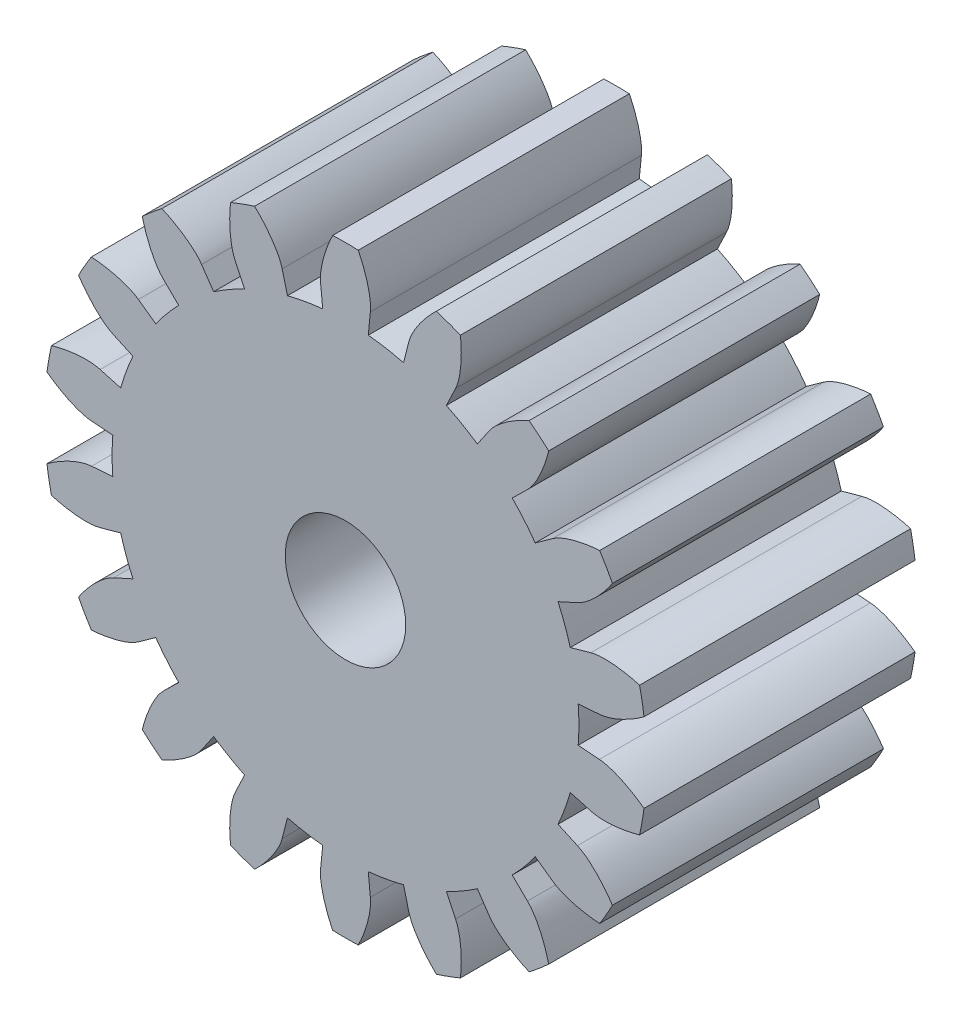
SolidWorks part; units mm, degrees
ref_plane "前视基准面" through (0, 0, 0) normal (0, 0, 1) x (1, 0, 0)
ref_plane "上视基准面" through (0, 0, 0) normal (0, 1, 0) x (1, 0, 0)
ref_plane "右视基准面" through (0, 0, 0) normal (1, 0, 0) x (0, 0, -1)
other "Configuration Table"
sketch "草图1" plane through (0, 0, 0) normal (0, 0, 1) x (1, 0, 0)
  line L0 (0, 0) -> (4.5, 0) construction
  line L1 (0, 0) -> (4.4829, 0.3922) construction
  line L2 (0, 0) -> (4.2162, 0.3242)
  line L3 (4.4829, 0.3922) -> (4.4829, -0.3922) construction
  line L4 (0, 0) -> (4.2162, -0.3242)
  circle A0 centre (0, 0) radius 5
  circle A1 centre (0, 0) radius 4.5 construction
  circle A2 centre (0, 0) radius 3.875
  circle A3 centre (0, 0) radius 4.2286 construction
  circle A4 centre (0, 0) radius 1
  spline S0 degree 4 poles (4.2162, 0.3242) (4.2483, 0.3267) (4.3375, 0.3403) (4.5024, 0.3926) (4.7554, 0.5133) (5.0556, 0.719) (5.3996, 1.035) (5.7429, 1.4621) (6.0488, 1.9801) (6.3604, 2.7282) (6.5454, 3.5193) (6.6174, 4.3594) (6.5658, 5.3616) (6.386, 6.3504) (6.0115, 7.457) (5.4105, 8.6071) (4.6509, 9.6584) (3.7565, 10.5972) (2.7501, 11.414) (1.6521, 12.1025) (0.4824, 12.659) (-0.5894, 13.0292) (-1.4522, 13.2437) (-2.0892, 13.3611) (-2.4865, 13.4209) (-2.8127, 13.4604) (-3.1237, 13.492) (-3.465, 13.5153) (-3.7294, 13.5295) (-4.0312, 13.5361) (-4.338, 13.5384) (-4.6432, 13.533) (-5.1827, 13.5111) (-5.559, 13.4725) (-5.9997, 13.426) (-6.2265, 13.3891) (-6.3687, 13.3688) (-6.431, 13.3583) knots 0 0 0 0 0 0.005604 0.015718 0.02996 0.048734 0.068727 0.096889 0.125051 0.153212 0.209535 0.237696 0.271429 0.327752 0.384075 0.440398 0.496721 0.553044 0.609367 0.66569 0.722013 0.778336 0.806497 0.820578 0.834659 0.84874 0.86282 0.876901 0.890982 0.900036 0.909091 0.931818 0.954545 0.977273 0.988636 1 1 1 1 1 construction
  spline S1 degree 4 poles (4.2162, 0.3242) (4.2483, 0.3267) (4.3375, 0.3403) (4.5024, 0.3926) (4.7554, 0.5133) (5.0556, 0.719) (5.3996, 1.035) (5.7429, 1.4621) (6.0488, 1.9801) (6.3604, 2.7282) (6.5454, 3.5193) (6.6174, 4.3594) (6.5658, 5.3616) (6.386, 6.3504) (6.0115, 7.457) (5.4105, 8.6071) (4.6509, 9.6584) (3.7565, 10.5972) (2.7501, 11.414) (1.6521, 12.1025) (0.4824, 12.659) (-0.5894, 13.0292) (-1.4522, 13.2437) (-2.0892, 13.3611) (-2.4865, 13.4209) (-2.8127, 13.4604) (-3.1237, 13.492) (-3.465, 13.5153) (-3.7294, 13.5295) (-4.0312, 13.5361) (-4.2111, 13.5375) (-4.3059, 13.5372) (-4.3531, 13.5368) knots 0 0 0 0 0 0.005604 0.015718 0.02996 0.048734 0.068727 0.096889 0.125051 0.153212 0.209535 0.237696 0.271429 0.327752 0.384075 0.440398 0.496721 0.553044 0.609367 0.66569 0.722013 0.778336 0.806497 0.820578 0.834659 0.84874 0.86282 0.876901 0.890982 0.900036 0.909091 0.909091 0.909091 0.909091 0.909091
  spline S2 degree 4 poles (4.2162, -0.3242) (4.2483, -0.3267) (4.3375, -0.3403) (4.5024, -0.3926) (4.7554, -0.5133) (5.0556, -0.719) (5.3996, -1.035) (5.7429, -1.4621) (6.0488, -1.9801) (6.3604, -2.7282) (6.5454, -3.5193) (6.6174, -4.3594) (6.5658, -5.3616) (6.386, -6.3504) (6.0115, -7.457) (5.4105, -8.6071) (4.6509, -9.6584) (3.7565, -10.5972) (2.7501, -11.414) (1.6521, -12.1025) (0.4824, -12.659) (-0.5894, -13.0292) (-1.4522, -13.2437) (-2.0892, -13.3611) (-2.4865, -13.4209) (-2.8127, -13.4604) (-3.1237, -13.492) (-3.465, -13.5153) (-3.7294, -13.5295) (-4.0312, -13.5361) (-4.338, -13.5384) (-4.6432, -13.533) (-5.1827, -13.5111) (-5.559, -13.4725) (-5.9997, -13.426) (-6.2265, -13.3891) (-6.3687, -13.3688) (-6.431, -13.3583) knots 0 0 0 0 0 0.005604 0.015718 0.02996 0.048734 0.068727 0.096889 0.125051 0.153212 0.209535 0.237696 0.271429 0.327752 0.384075 0.440398 0.496721 0.553044 0.609367 0.66569 0.722013 0.778336 0.806497 0.820578 0.834659 0.84874 0.86282 0.876901 0.890982 0.900036 0.909091 0.931818 0.954545 0.977273 0.988636 1 1 1 1 1 construction
  spline S3 degree 4 poles (4.2162, -0.3242) (4.2483, -0.3267) (4.3375, -0.3403) (4.5024, -0.3926) (4.7554, -0.5133) (5.0556, -0.719) (5.3996, -1.035) (5.7429, -1.4621) (6.0488, -1.9801) (6.3604, -2.7282) (6.5454, -3.5193) (6.6174, -4.3594) (6.5658, -5.3616) (6.386, -6.3504) (6.0115, -7.457) (5.4105, -8.6071) (4.6509, -9.6584) (3.7565, -10.5972) (2.7501, -11.414) (1.6521, -12.1025) (0.4824, -12.659) (-0.5894, -13.0292) (-1.4522, -13.2437) (-2.0892, -13.3611) (-2.4865, -13.4209) (-2.8127, -13.4604) (-3.1237, -13.492) (-3.465, -13.5153) (-3.7294, -13.5295) (-4.0312, -13.5361) (-4.2111, -13.5375) (-4.3059, -13.5372) (-4.3531, -13.5368) knots 0 0 0 0 0 0.005604 0.015718 0.02996 0.048734 0.068727 0.096889 0.125051 0.153212 0.209535 0.237696 0.271429 0.327752 0.384075 0.440398 0.496721 0.553044 0.609367 0.66569 0.722013 0.778336 0.806497 0.820578 0.834659 0.84874 0.86282 0.876901 0.890982 0.900036 0.909091 0.909091 0.909091 0.909091 0.909091
  point P15 (4.4829, 0)
  dimension "齿顶圆直径" = 10
  dimension "分度圆直径" = 9
  dimension "齿根圆直径" = 7.75
  dimension "基圆直径" = 8.4572
  dimension "内孔直径" = 2
  dimension "渐近线镜像线夹角" = 5
extrude "凸台-拉伸1" add sketch "草图1" along normal blind 4.5 contours A0 | A4
extrude "切除-拉伸1" cut sketch "草图1<3>" along normal through all contours A2 S3 A0 S1 region at (4.5106, 0, 0)
sketch "草图1<3>" plane through (0, 0, 0) normal (0, 0, 1) x (1, 0, 0) same geometry as "草图1"
pattern_circular "阵列(圆周)1" count 18 every 20 about axis through (0, 0, 4.5) along (0, 0, 1) of "切除-拉伸1"
equation "\"m\"= 0.5'模数"
equation "\"z\" = 18'齿数"
equation "\"a\"= 20度'压力角"
equation "\"d\"= \"m\" * \"z\"'分度圆直径"
equation "\"da\"= ( \"z\" + 2 ) * \"m\"'齿顶圆直径"
equation "\"df\"= ( \"z\" - 2.5 ) * \"m\"'齿根圆直径"
equation "\"s\"= 0.5 * PI * \"m\"'分度圆齿厚"
equation "\"r\"= 0.38 * \"m\"'齿根圆角"
equation "\"B\"= 0.3 * \"d\"'齿厚"
equation "\"db\"= \"m\" * \"z\" * cos ( \"a\" )'基圆直径"
equation "\"rb\"= \"db\" / 2'基圆半径"
equation "\"齿顶圆直径@草图1\"= \"da\""
equation "\"分度圆直径@草图1\"= \"d\""
equation "\"齿根圆直径@草图1\"= \"df\""
equation "\"基圆直径@草图1\"= \"db\""
equation "\"渐近线镜像线夹角@草图1\"= 360 / 4 / \"z\""
equation "\"h\"= 4.5'齿轮厚度"
equation "\"ir\"= 2'内孔直径"
equation "\"内孔直径@草图1\"= \"ir\""
equation "\"齿轮厚@凸台-拉伸1\"= \"h\""
equation "\"齿轮夹角@阵列(圆周)1\"= 360 / \"z\""
equation "\"齿数@阵列(圆周)1\"= \"z\""
